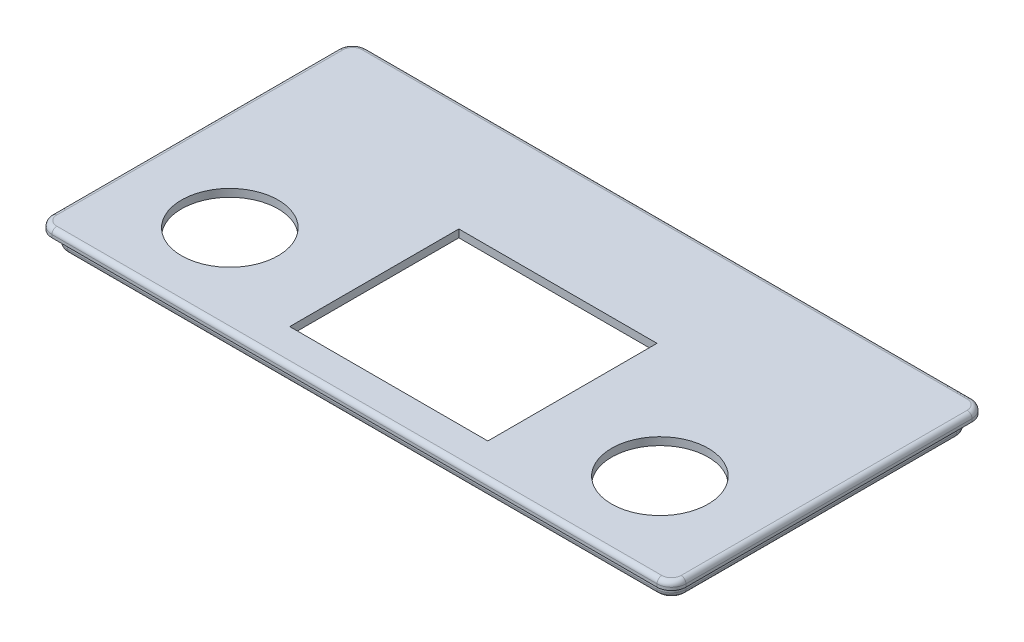
SolidWorks part; units mm, degrees
ref_plane "Спереди" through (0, 0, 0) normal (0, 0, 1) x (1, 0, 0)
ref_plane "Сверху" through (0, 0, 0) normal (0, 1, 0) x (1, 0, 0)
ref_plane "Справа" through (0, 0, 0) normal (1, 0, 0) x (0, 0, -1)
sketch "Sketch1" plane through (0, 0, 0) normal (0, 1, 0) x (1, 0, 0)
  line L0 (-62.4, -29.4) -> (-62.4, 29.4)
  line L1 (-64, -31) -> (64, -31)
  line L2 (-64, -31) -> (-64, 31)
  line L3 (-64, 31) -> (64, 31)
  line L4 (64, -31) -> (64, 31)
  line L5 (-64, -31) -> (64, 31) construction
  line L6 (-64, 31) -> (64, -31) construction
  line L7 (-62.4, 29.4) -> (62.4, 29.4)
  line L8 (62.4, -29.4) -> (62.4, 29.4)
  line L9 (-62.4, -29.4) -> (62.4, -29.4)
  point P0 (0, 0)
  dimension "D1" = 128
  dimension "D2" = 62
  dimension "D3" = 1.6
extrude "Boss-Extrude1" add sketch "Sketch1" along normal blind 3
sketch "Sketch3" plane through (0, 3, 0) normal (0, 1, 0) x (1, 0, 0)
  line L24 (65.6, -32.6) -> (65.6, 32.6)
  line L25 (-65.6, -32.6) -> (65.6, -32.6)
  line L26 (-65.6, 32.6) -> (-65.6, -32.6)
  line L27 (65.6, 32.6) -> (-65.6, 32.6)
  line L28 (65.6, -32.6) -> (65.6, 32.6)
  line L29 (-65.6, -32.6) -> (65.6, -32.6)
  line L30 (-65.6, 32.6) -> (-65.6, -32.6)
  line L31 (65.6, 32.6) -> (-65.6, 32.6)
  dimension "D1" = 1.6
extrude "Boss-Extrude3" add sketch "Sketch3" along normal blind 1.6
fillet "Fillet2" radius 3 12 edges at (-62.4, 1.5, 29.4) (-62.4, 1.5, -29.4) (62.4, 1.5, -29.4) (62.4, 1.5, 29.4) (64, 1.5, -31) (65.6, 3.8, -32.6) (65.6, 3.8, 32.6) (64, 1.5, 31) (-64, 1.5, -31) (-65.6, 3.8, -32.6) (-65.6, 3.8, 32.6) (-64, 1.5, 31)
sketch "Sketch4" plane through (0, 4.6, 0) normal (0, 1, 0) x (1, 0, 0)
  circle A0 centre (-44.3929, -14) radius 10
  circle A1 centre (44.6071, -14) radius 10
  dimension "D1" = 20
extrude "Cut-Extrude1" cut sketch "Sketch4" against normal up to next
fillet "Fillet3" radius 1 8 edges at (64.7213, 4.6, -31.7213) (65.6, 4.6, 0) (64.7213, 4.6, 31.7213) (0, 4.6, 32.6) (-64.7213, 4.6, 31.7213) (-65.6, 4.6, 0) (-64.7213, 4.6, -31.7213) (0, 4.6, -32.6)
fillet "Fillet4" radius 1 8 edges at (-63.1213, 0, 30.1213) (-64, 0, 0) (-63.1213, 0, -30.1213) (0, 0, -31) (63.1213, 0, -30.1213) (64, 0, 0) (63.1213, 0, 30.1213) (0, 0, 31)
sketch "Sketch5" plane through (0, 4.6, 0) normal (0, 1, 0) x (1, 0, 0)
  line L1 (-20.5, -25.5) -> (20.5, -25.5)
  line L2 (-20.5, -25.5) -> (-20.5, 9.5)
  line L3 (-20.5, 9.5) -> (20.5, 9.5)
  line L4 (20.5, -25.5) -> (20.5, 9.5)
  line L5 (-20.5, -25.5) -> (20.5, 9.5) construction
  line L6 (-20.5, 9.5) -> (20.5, -25.5) construction
  circle A0 centre (-44.3929, -14) radius 10 construction
  point P0 (0, -8)
  dimension "D3" = 6
  dimension "D1" = 35
  dimension "D2" = 41
extrude "Cut-Extrude2" cut sketch "Sketch5" against normal up to next
